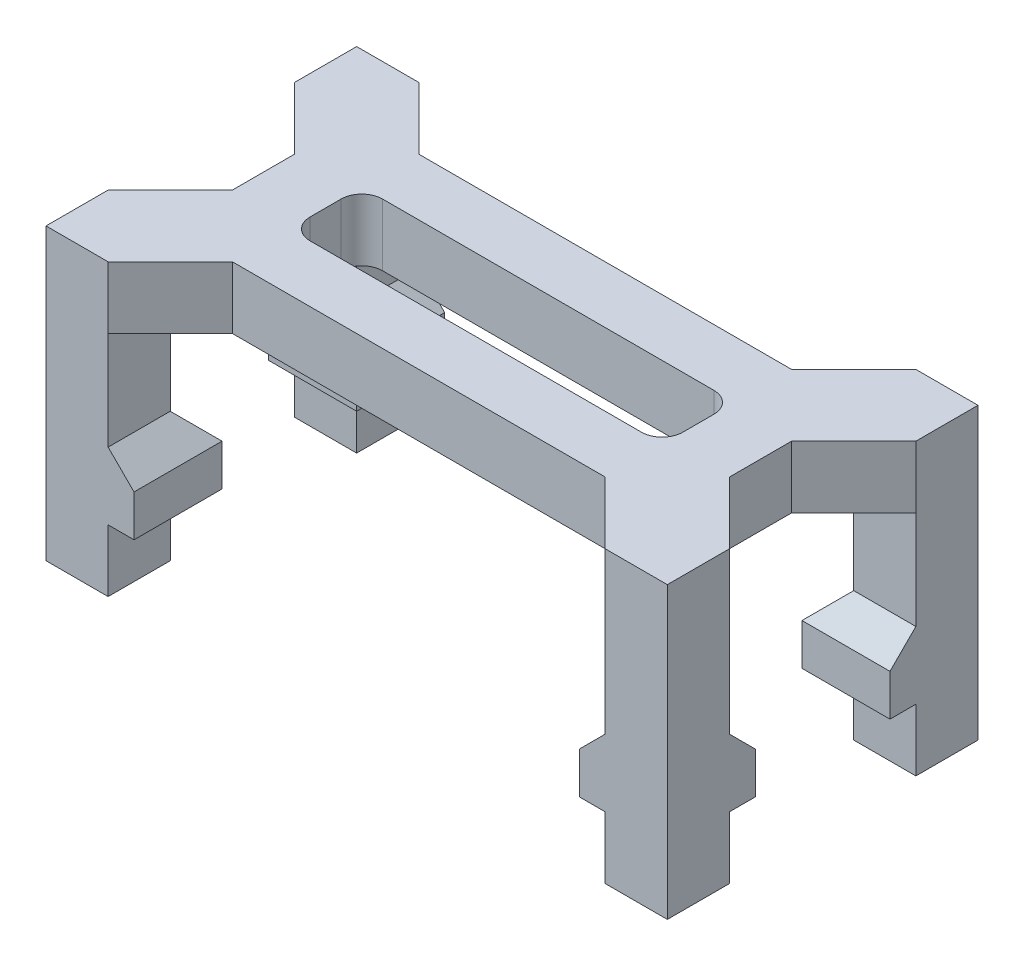
SolidWorks part; units mm, degrees
ref_plane "Front Plane" through (0, 0, 0) normal (0, 0, 1) x (1, 0, 0)
ref_plane "Top Plane" through (0, 0, 0) normal (0, 1, 0) x (1, 0, 0)
ref_plane "Right Plane" through (0, 0, 0) normal (1, 0, 0) x (0, 0, -1)
sketch "Sketch1" plane through (0, 0, 0) normal (0, 1, 0) x (1, 0, 0)
  line L0 (-15, 0) -> (15, 0) construction
  line L1 (-15, 7.5) -> (15, 7.5) construction
  line L2 (-15, 7.5) -> (-15, -7.5) construction
  line L3 (-15, -7.5) -> (15, -7.5) construction
  line L4 (15, 7.5) -> (15, -7.5) construction
  line L5 (-15, 7.5) -> (-12, 7.5)
  line L6 (-15, 7.5) -> (-15, 4.5)
  line L7 (-15, 4.5) -> (-12, 4.5)
  line L8 (-12, 7.5) -> (-12, 4.5)
  line L9 (0, 7.5) -> (0, -7.5) construction
  line L10 (15, 4.5) -> (12, 4.5)
  line L11 (12, 7.5) -> (12, 4.5)
  line L12 (15, 7.5) -> (12, 7.5)
  line L13 (15, 7.5) -> (15, 4.5)
  line L14 (15, -7.5) -> (15, -4.5)
  line L15 (15, -7.5) -> (12, -7.5)
  line L16 (12, -7.5) -> (12, -4.5)
  line L17 (15, -4.5) -> (12, -4.5)
  line L18 (-15, -4.5) -> (-12, -4.5)
  line L19 (-12, -7.5) -> (-12, -4.5)
  line L20 (-15, -7.5) -> (-12, -7.5)
  line L21 (-15, -7.5) -> (-15, -4.5)
  point P4 (0, 7.5)
  point P6 (-15, 0)
  dimension "D1" = 30
  dimension "D2" = 15
  dimension "D3" = 3
extrude "Boss-Extrude1" add sketch "Sketch1" along normal blind 8
sketch "Sketch2" plane through (0, 8, 0) normal (0, 1, 0) x (1, 0, 0)
  line L1 (-15, -7.5) -> (15, -7.5)
  line L2 (-15, -7.5) -> (-15, 7.5)
  line L3 (-15, 7.5) -> (15, 7.5)
  line L4 (15, -7.5) -> (15, 7.5)
extrude "Boss-Extrude2" add sketch "Sketch2" along normal blind 3
sketch "Sketch3" plane through (0, 11, 0) normal (0, 1, 0) x (1, 0, 0)
  line L0 (-15, 0) -> (15, 0) construction
  line L1 (-15, 7.5) -> (-15, -7.5) construction
  line L2 (15, -7.5) -> (15, 7.5) construction
  line L3 (0, 7.5) -> (0, -7.5) construction
  line L4 (15, 7.5) -> (-15, 7.5) construction
  line L5 (-15, -7.5) -> (15, -7.5) construction
  line L6 (-12, 7.5) -> (-9, 4.5)
  line L7 (-9, 4.5) -> (9, 4.5)
  line L8 (-12, 7.5) -> (12, 7.5)
  line L9 (12, 7.5) -> (9, 4.5)
  line L10 (-12, -7.5) -> (-9, -4.5)
  line L11 (-9, -4.5) -> (9, -4.5)
  line L12 (12, -7.5) -> (9, -4.5)
  line L13 (-12, -7.5) -> (12, -7.5)
  line L14 (-15, 4.5) -> (-12, 1.5)
  line L15 (-12, 1.5) -> (-12, -1.5)
  line L16 (-15, 4.5) -> (-15, -4.5)
  line L17 (-15, -4.5) -> (-12, -1.5)
  line L18 (15, 4.5) -> (12, 1.5)
  line L19 (15, 4.5) -> (15, -4.5)
  line L20 (15, -4.5) -> (12, -1.5)
  line L21 (12, 1.5) -> (12, -1.5)
  point P18 (0, 4.5)
  point P26 (-12, 0)
  dimension "D1" = 3
  dimension "D2" = 3
  dimension "D3" = 45
  dimension "D4" = 45
  dimension "D5" = 3
  dimension "D6" = 3
extrude "Cut-Extrude1" cut sketch "Sketch3" against normal through all
sketch "Sketch4" plane through (0, 11, 0) normal (0, 1, 0) x (1, 0, 0)
  line L1 (-8, 1.75) -> (8, 1.75)
  line L2 (-9, 0.75) -> (-9, -0.75)
  line L3 (-8, -1.75) -> (8, -1.75)
  line L4 (9, 0.75) -> (9, -0.75)
  arc A0 (8, 1.75) -> (9, 0.75) centre (8, 0.75) cw
  arc A1 (8, -1.75) -> (9, -0.75) centre (8, -0.75) ccw
  arc A2 (-9, -0.75) -> (-8, -1.75) centre (-8, -0.75) ccw
  arc A3 (-8, 1.75) -> (-9, 0.75) centre (-8, 0.75) ccw
  point P9 (0, 1.75)
  point P11 (-9, 0)
  point P12 (9, 1.75)
  point P19 (-9, 1.75)
  dimension "D2" = 1
  dimension "D1" = 18
  dimension "D3" = 1.5
extrude "Cut-Extrude2" cut sketch "Sketch4" against normal through all
sketch "Sketch6" plane through (0, 0, 0) normal (0, -1, 0) x (1, 0, 0)
  line L0 (-15, 4.5) -> (-15, 7.5) construction
  line L1 (-12, 7.5) -> (-10.75, 7.5)
  line L2 (-12, 7.5) -> (-12, 4.5)
  line L4 (-10.75, 7.5) -> (-10.75, 4.5)
  line L5 (0, 4.5) -> (0, -4.5) construction
  line L6 (-12, 4.5) -> (-15, 4.5)
  line L8 (-12, 3.25) -> (-15, 3.25)
  line L9 (-15, 4.5) -> (-15, 3.25)
  line L10 (-12, 3.25) -> (-10.75, 3.25)
  line L13 (-10.75, 3.25) -> (-10.75, 4.5)
  line L14 (-9, 4.5) -> (9, 4.5) construction
  line L15 (9, -4.5) -> (-9, -4.5) construction
  line L16 (-12, 0) -> (12, 0) construction
  line L17 (-12, -1.5) -> (-12, 1.5) construction
  line L18 (12, 1.5) -> (12, -1.5) construction
  line L19 (12, 7.5) -> (10.75, 7.5)
  line L20 (10.75, 7.5) -> (10.75, 4.5)
  line L21 (10.75, 3.25) -> (10.75, 4.5)
  line L22 (12, 3.25) -> (10.75, 3.25)
  line L23 (12, 3.25) -> (15, 3.25)
  line L24 (15, 4.5) -> (15, 3.25)
  line L25 (12, 4.5) -> (15, 4.5)
  line L26 (12, 7.5) -> (12, 4.5)
  line L31 (12, -7.5) -> (12, -4.5)
  line L32 (12, -4.5) -> (15, -4.5)
  line L33 (15, -4.5) -> (15, -3.25)
  line L34 (12, -3.25) -> (15, -3.25)
  line L35 (12, -3.25) -> (10.75, -3.25)
  line L36 (10.75, -3.25) -> (10.75, -4.5)
  line L37 (10.75, -7.5) -> (10.75, -4.5)
  line L38 (12, -7.5) -> (10.75, -7.5)
  line L39 (-12, -7.5) -> (-10.75, -7.5)
  line L40 (-10.75, -7.5) -> (-10.75, -4.5)
  line L41 (-10.75, -3.25) -> (-10.75, -4.5)
  line L42 (-12, -3.25) -> (-10.75, -3.25)
  line L43 (-12, -3.25) -> (-15, -3.25)
  line L44 (-15, -4.5) -> (-15, -3.25)
  line L45 (-12, -4.5) -> (-15, -4.5)
  line L46 (-12, -7.5) -> (-12, -4.5)
  dimension "D1" = 1.25
  dimension "D2" = 1.25
extrude "Boss-Extrude3" add sketch "Sketch6" against normal blind 2
chamfer "Chamfer1" distance 1.25 angle 45 8 edges at (-12, 2, 6) (-13.5, 2, 4.5) (-13.5, 2, -4.5) (-12, 2, -6) (12, 2, 6) (13.5, 2, 4.5) (12, 2, -6) (13.5, 2, -4.5)
sketch "Sketch7" plane through (0, 0, 0) normal (0, -1, 0) x (1, 0, 0)
  line L1 (-15, 7.5) -> (-12, 7.5)
  line L2 (-15, 7.5) -> (-15, 4.5)
  line L3 (-15, 4.5) -> (-12, 4.5)
  line L4 (-12, 7.5) -> (-12, 4.5)
  line L5 (-15, -7.5) -> (-12, -7.5)
  line L6 (-15, -7.5) -> (-15, -4.5)
  line L7 (-15, -4.5) -> (-12, -4.5)
  line L8 (-12, -7.5) -> (-12, -4.5)
  line L9 (15, -7.5) -> (12, -7.5)
  line L10 (15, -7.5) -> (15, -4.5)
  line L11 (15, -4.5) -> (12, -4.5)
  line L12 (12, -7.5) -> (12, -4.5)
  line L13 (15, 7.5) -> (12, 7.5)
  line L14 (15, 7.5) -> (15, 4.5)
  line L15 (15, 4.5) -> (12, 4.5)
  line L16 (12, 7.5) -> (12, 4.5)
  dimension "D1" = 3
extrude "Boss-Extrude4" add sketch "Sketch7" along normal blind 3
